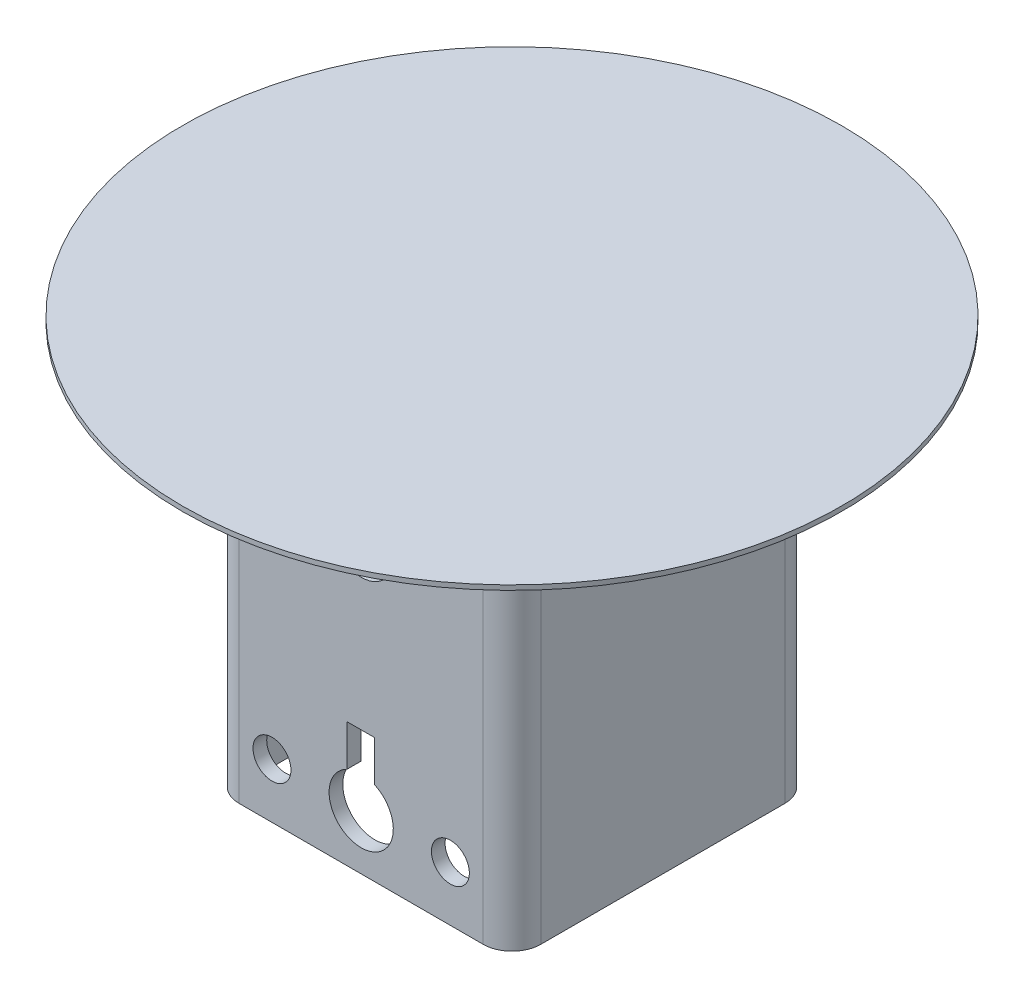
SolidWorks part; units mm, degrees
ref_plane "Front Plane" through (0, 0, 0) normal (0, 0, 1) x (1, 0, 0)
ref_plane "Top Plane" through (0, 0, 0) normal (0, 1, 0) x (1, 0, 0)
ref_plane "Right Plane" through (0, 0, 0) normal (1, 0, 0) x (0, 0, -1)
sketch "Sketch1" plane through (0, 0, 0) normal (1, 0, 0) x (0, 0, -1)
  line L0 (0, 304.8) -> (0, -304.8)
  dimension "D1" = 609.6
surface "Surface-Extrude1" [suppressed] sketch "Sketch1" parameters "D1"=609.6
sketch "Sketch3" plane through (0, 0, 0) normal (0, 0, 1) x (1, 0, 0)
  line L0 (-195.1803, -229.4219) -> (-233.3854, -229.4219) construction
  line L1 (-195.1803, -229.9735) -> (-156.9752, -229.9735)
  line L2 (-195.1803, -229.9735) -> (-195.1803, -229.4219)
  line L3 (-195.1803, -229.4219) -> (-156.9752, -229.4219)
  line L4 (-156.9752, -229.9735) -> (-156.9752, -229.4219)
  dimension "D1" = 38.2051
revolve "Revolve1" add sketch "Sketch3" angle 360 about L2
sketch "Sketch4" plane through (0, -229.9735, 0) normal (0, -1, 0) x (1, 0, 0)
  line L0 (-211.076, -13.3557) -> (-211.076, 13.3557)
  line L1 (-209.3298, -17.4832) -> (-181.0308, -17.4832)
  line L2 (-212.6635, -14.1495) -> (-212.6635, 14.1495)
  line L3 (-209.3298, 17.4832) -> (-181.0308, 17.4832)
  line L4 (-177.6971, -14.1495) -> (-177.6971, 14.1495)
  line L5 (-212.6635, -17.4832) -> (-177.6971, 17.4832) construction
  line L6 (-212.6635, 17.4832) -> (-177.6971, -17.4832) construction
  line L7 (-208.536, 15.8957) -> (-181.8246, 15.8957)
  line L8 (-179.2846, -13.3557) -> (-179.2846, 13.3557)
  line L9 (-208.536, -15.8957) -> (-181.8246, -15.8957)
  line L10 (-211.076, -15.8957) -> (-211.076, 15.8957) construction
  line L11 (-211.076, -15.8957) -> (-179.2846, -15.8957) construction
  line L12 (-179.2846, -15.8957) -> (-179.2846, 15.8957) construction
  line L13 (-211.076, 15.8957) -> (-179.2846, 15.8957) construction
  line L14 (-212.6635, -17.4832) -> (-177.6971, -17.4832) construction
  line L15 (-212.6635, -17.4832) -> (-212.6635, 17.4832) construction
  line L16 (-177.6971, -17.4832) -> (-177.6971, 17.4832) construction
  line L17 (-212.6635, 17.4832) -> (-177.6971, 17.4832) construction
  circle A0 centre (-195.1803, 0) radius 38.2051 construction
  arc A1 (-211.076, -13.3557) -> (-208.536, -15.8957) centre (-208.536, -13.3557) ccw
  arc A2 (-179.2846, -13.3557) -> (-181.8246, -15.8957) centre (-181.8246, -13.3557) cw
  arc A3 (-181.8246, 15.8957) -> (-179.2846, 13.3557) centre (-181.8246, 13.3557) cw
  arc A4 (-211.076, 13.3557) -> (-208.536, 15.8957) centre (-208.536, 13.3557) cw
  arc A5 (-209.3298, -17.4832) -> (-212.6635, -14.1495) centre (-209.3298, -14.1495) cw
  arc A6 (-181.0308, -17.4832) -> (-177.6971, -14.1495) centre (-181.0308, -14.1495) ccw
  arc A7 (-181.0308, 17.4832) -> (-177.6971, 14.1495) centre (-181.0308, 14.1495) cw
  arc A8 (-212.6635, 14.1495) -> (-209.3298, 17.4832) centre (-209.3298, 14.1495) cw
  point P0 (-195.1803, 0)
  dimension "D2" = 2.54
  dimension "D3" = 3.3337
  dimension "D1" = 1.5875
extrude "Boss-Extrude1" add sketch "Sketch4" along normal blind 46.736
sketch "Sketch5" plane through (0, 0, 0) normal (0, 0, 1) x (1, 0, 0)
  line L8 (-209.3298, -276.7095) -> (-209.3298, -229.9735) construction
  line L9 (-181.0308, -276.7095) -> (-181.0308, -229.9735) construction
  line L10 (-181.0308, -276.7095) -> (-209.3298, -276.7095) construction
  line L11 (-181.0308, -229.9735) -> (-209.3298, -229.9735) construction
  line L12 (-196.814, -239.4985) -> (-205.5198, -239.4985) construction
  line L14 (-196.814, -267.0151) -> (-196.814, -262.2471)
  line L15 (-196.814, -262.2471) -> (-193.6189, -262.2471)
  line L16 (-184.8408, -239.4985) -> (-193.6189, -239.4985) construction
  line L17 (-205.5198, -239.4985) -> (-205.5198, -270.3595) construction
  line L18 (-205.5198, -270.3595) -> (-184.8408, -270.3595) construction
  line L19 (-184.8408, -270.3595) -> (-184.8408, -239.4985) construction
  line L20 (-193.6189, -267.0151) -> (-193.6189, -262.2471)
  line L22 (-196.814, -239.8642) -> (-196.814, -235.0963)
  line L23 (-196.814, -235.0963) -> (-193.6189, -235.0963)
  line L24 (-193.6189, -239.8642) -> (-193.6189, -235.0963)
  circle A0 centre (-205.5198, -270.3595) radius 2.2008
  circle A1 centre (-205.5198, -239.4985) radius 2.2008
  circle A2 centre (-184.8408, -239.4985) radius 2.2008
  circle A3 centre (-184.8408, -270.3595) radius 2.2008
  arc A4 (-196.814, -239.8642) -> (-193.6189, -239.8298) centre (-195.1803, -243.2087) ccw
  arc A5 (-196.814, -267.0151) -> (-193.6189, -266.9807) centre (-195.1803, -270.3595) ccw
  dimension "D1" = 3.81
  dimension "D2" = 3.81
  dimension "D3" = 6.35
  dimension "D4" = 9.525
extrude "Cut-Extrude1" cut sketch "Sketch5" against normal through all and the other way through all contours A1 | L22 A4 L24 L23 | A2 | A0 | L14 A5 L20 L15 | A3 region at (-195.1898, -268.9032, 0) region at (-195.1898, -241.7523, 0) region at (-205.5198, -270.3595, 0) region at (-205.5198, -239.4985, 0) region at (-184.8408, -239.4985, 0) region at (-184.8408, -270.3595, 0)
scale "Scale1" bodies to scale 116 102 scale about origin uniform scaling yes scale factor 2.102564
